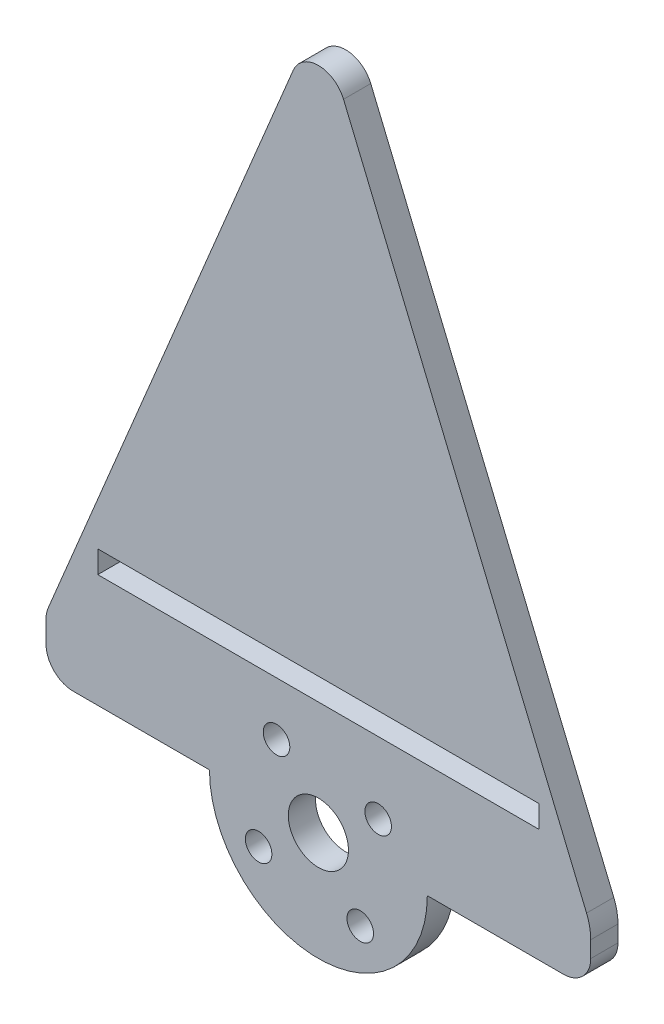
SolidWorks part; units mm, degrees
ref_plane "Front Plane" through (0, 0, 0) normal (0, 0, 1) x (1, 0, 0)
ref_plane "Top Plane" through (0, 0, 0) normal (0, 1, 0) x (1, 0, 0)
ref_plane "Right Plane" through (0, 0, 0) normal (1, 0, 0) x (0, 0, -1)
sketch "Sketch1" plane through (0, 0, 0) normal (0, 0, 1) x (1, 0, 0)
  line L0 (0, 0) -> (0, 76.2) construction
  line L1 (-31.75, 0) -> (-31.75, -6.35)
  line L2 (0, 76.2) -> (-31.75, 0)
  line L3 (-31.75, -6.35) -> (-12.7, -6.35)
  line L4 (31.75, -6.35) -> (12.7, -6.35)
  line L5 (31.75, 0) -> (31.75, -6.35)
  line L6 (0, 76.2) -> (31.75, 0)
  arc A0 (-12.7, -6.35) -> (12.7, -6.35) centre (0, -6.35) ccw
  dimension "D3" = 12.7
  dimension "D1" = 31.75
  dimension "D2" = 76.2
  dimension "D4" = 6.35
  dimension "D5" = 12.7
extrude "Boss-Extrude1" add sketch "Sketch1" along normal blind 3.175
fillet "Fillet4" radius 3.175 1 edges at (-31.75, -6.35, 1.5875) type face fillet first side face at (-22.225, -6.35, 1.5875) second side face at (-31.75, -3.175, 1.5875)
fillet "Fillet5" radius 3.175 1 edges at (-31.75, 0, 1.5875) type face fillet first side face at (-15.875, 38.1, 1.5875) second side face at (-31.75, -1.5875, 1.5875)
fillet "Fillet6" radius 3.175 1 edges at (0, 76.2, 1.5875) type face fillet first side face at (-15.7529, 38.3931, 1.5875) second side face at (15.875, 38.1, 1.5875)
fillet "Fillet7" radius 6.35 1 edges at (31.75, 0, 1.5875) type face fillet first side face at (17.3404, 34.5831, 1.5875) second side face at (31.75, -3.175, 1.5875)
fillet "Fillet8" radius 3.175 1 edges at (31.75, -6.35, 1.5875) type face fillet first side face at (31.75, -3.81, 1.5875) second side face at (22.225, -6.35, 1.5875)
sketch "Sketch2" plane through (0, 0, 3.175) normal (0, 0, 1) x (1, 0, 0)
  line L0 (-12.7, -6.35) -> (12.7, -6.35) construction
  line L1 (4.8806, -13.3202) -> (-4.8806, 0.6202) construction
  line L2 (0, -6.35) -> (0, -3.7657) construction
  line L3 (0, -6.35) -> (6.9702, -1.4694) construction
  circle A0 centre (0, -6.35) radius 3.5052
  circle A1 centre (-4.8806, 0.6202) radius 1.5494
  circle A2 centre (4.8806, -13.3202) radius 1.5494
  circle A3 centre (6.9702, -1.4694) radius 1.5494
  circle A4 centre (-6.9702, -11.2306) radius 1.5494
  dimension "D1" = 7.0104
  dimension "D3" = 3.0988
  dimension "D6" = 3.0988
  dimension "D2" = 8.509
  dimension "D4" = 55
  dimension "D5" = 8.509
extrude "Cut-Extrude1" cut sketch "Sketch2" against normal through all
sketch "Sketch4" plane through (0, 0, 3.175) normal (0, 0, 1) x (1, 0, 0)
  line L1 (25.7175, 6.8532) -> (-25.7175, 6.8532)
  line L2 (25.7175, 6.8532) -> (25.7175, 9.4567)
  line L3 (25.7175, 9.4567) -> (-25.7175, 9.4567)
  line L4 (-25.7175, 6.8532) -> (-25.7175, 9.4567)
  line L5 (25.7175, 6.8532) -> (-25.7175, 9.4567) construction
  line L6 (25.7175, 9.4567) -> (-25.7175, 6.8532) construction
  circle A0 centre (0, -6.35) radius 3.5052 construction
  point P0 (0, 8.155)
  dimension "D1" = 14.505
  dimension "D2" = 51.435
  dimension "D3" = 2.6035
extrude "Cut-Extrude2" cut sketch "Sketch4" against normal through all
sketch "Sketch5" plane through (0, 0, 3.175) normal (0, 0, 1) x (1, 0, 0)
  line L0 (-27.8097, 9.4567) -> (27.8097, 9.4567) construction
  line L1 (-2.9308, 69.1662) -> (-31.5058, 0.5862) construction
  line L2 (31.2615, 1.1723) -> (2.9308, 69.1662) construction
  line L3 (25.7175, 9.4567) -> (-25.7175, 9.4567) construction
  dimension "D1" = 55.6194
